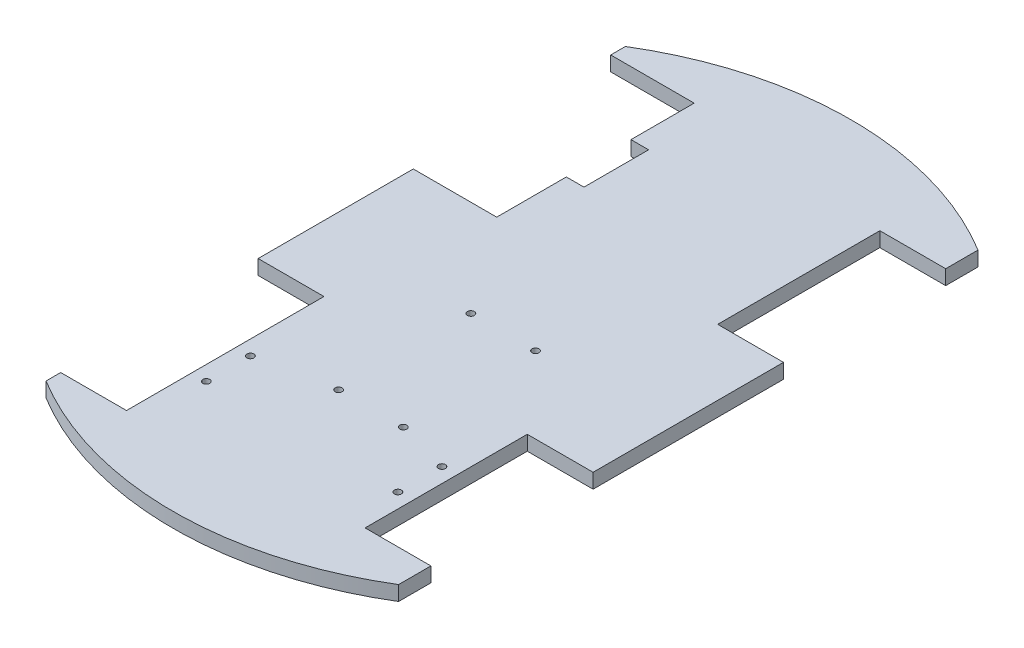
SolidWorks part; units mm, degrees
material "Oak"
ref_plane "Front Plane" through (0, 0, 0) normal (0, 0, 1) x (1, 0, 0)
ref_plane "Top Plane" through (0, 0, 0) normal (0, 1, 0) x (1, 0, 0)
ref_plane "Right Plane" through (0, 0, 0) normal (1, 0, 0) x (0, 0, -1)
sketch "Sketch1" plane through (0, 0, 0) normal (0, 1, 0) x (1, 0, 0)
  line L0 (50.292, 32.512) -> (76.2, 32.512) construction
  line L1 (-76.2, 32.512) -> (-50.292, 32.512) construction
  line L2 (-76.2, 32.512) -> (-76.2, -32.512) construction
  line L3 (-76.2, -32.512) -> (-50.292, -32.512) construction
  line L4 (-50.292, 32.512) -> (-50.292, -32.512) construction
  line L5 (-76.2, 32.512) -> (-50.292, -32.512) construction
  line L6 (-76.2, -32.512) -> (-50.292, 32.512) construction
  line L7 (50.292, 32.512) -> (50.292, -32.512) construction
  line L8 (50.292, -32.512) -> (76.2, -32.512) construction
  line L9 (76.2, 32.512) -> (76.2, -32.512) construction
  line L10 (50.292, 32.512) -> (76.2, -32.512) construction
  line L11 (50.292, -32.512) -> (76.2, 32.512) construction
  line L12 (-76.2, -119.888) -> (-50.292, -119.888) construction
  line L13 (-76.2, -119.888) -> (-76.2, -184.912) construction
  line L14 (-76.2, -184.912) -> (-50.292, -184.912) construction
  line L15 (-50.292, -119.888) -> (-50.292, -184.912) construction
  line L16 (-76.2, -119.888) -> (-50.292, -184.912) construction
  line L17 (-76.2, -184.912) -> (-50.292, -119.888) construction
  line L18 (50.292, -119.888) -> (76.2, -119.888) construction
  line L19 (50.292, -119.888) -> (50.292, -184.912) construction
  line L20 (50.292, -184.912) -> (76.2, -184.912) construction
  line L21 (76.2, -119.888) -> (76.2, -184.912) construction
  line L22 (50.292, -119.888) -> (76.2, -184.912) construction
  line L23 (50.292, -184.912) -> (76.2, -119.888) construction
  line L24 (-76.2, -42.672) -> (-40.132, -42.672)
  line L25 (-76.2, 0) -> (76.2, 0) construction
  line L26 (-76.2, 0) -> (-76.2, -152.4) construction
  line L27 (-76.2, -152.4) -> (76.2, -152.4) construction
  line L28 (76.2, 0) -> (76.2, -152.4) construction
  line L29 (-76.2, 0) -> (76.2, -152.4) construction
  line L30 (-76.2, -152.4) -> (76.2, 0) construction
  line L31 (-40.132, 42.672) -> (-40.132, -42.672)
  line L32 (-76.2, 42.672) -> (-40.132, 42.672)
  line L33 (47.752, -35.052) -> (76.2, -35.052)
  line L34 (47.752, 35.052) -> (47.752, -35.052)
  line L35 (47.752, 35.052) -> (76.2, 35.052)
  line L36 (47.752, -187.452) -> (76.2, -187.452)
  line L37 (47.752, -117.348) -> (47.752, -187.452)
  line L38 (47.752, -117.348) -> (76.2, -117.348)
  line L39 (-76.2, -195.072) -> (-47.752, -195.072)
  line L40 (-47.752, -109.728) -> (-47.752, -195.072)
  line L41 (-76.2, -109.728) -> (-47.752, -109.728)
  line L42 (-76.2, -109.728) -> (-76.2, -42.672)
  line L43 (76.2, -35.052) -> (76.2, -117.348)
  line L44 (-76.2, 42.672) -> (-76.2, 49.022)
  line L45 (76.2, 35.052) -> (76.2, 49.022)
  line L46 (-76.2, -195.072) -> (-76.2, -201.422)
  line L47 (76.2, -187.452) -> (76.2, -201.422)
  line L48 (0, 0) -> (0, 19.7922) construction
  line L49 (-32.512, 15.3535) -> (-40.132, 15.3535)
  line L50 (-32.512, 15.3535) -> (-32.512, -12.5865)
  line L51 (-32.512, -12.5865) -> (-40.132, -12.5865)
  line L52 (-40.132, 15.3535) -> (-40.132, -12.5865)
  line L53 (-32.512, 15.3535) -> (-40.132, -12.5865) construction
  line L54 (-32.512, -12.5865) -> (-40.132, 15.3535) construction
  line L55 (32.512, -12.5865) -> (40.132, -12.5865)
  line L56 (32.512, 15.3535) -> (32.512, -12.5865)
  line L57 (32.512, 15.3535) -> (40.132, 15.3535)
  arc A0 (-76.2, 49.022) -> (76.2, 49.022) centre (0, -76.2) cw
  arc A1 (-76.2, -201.422) -> (76.2, -201.422) centre (0, -76.2) ccw
  point P4 (-63.246, 0)
  point P9 (63.246, 0)
  point P14 (-63.246, -152.4)
  point P19 (63.246, -152.4)
  point P24 (0, -76.2)
  point P52 (-36.322, 1.3835)
  dimension "D7" = 6.35
  dimension "D8" = 7.62
  dimension "D12" = 146.5844
  dimension "D1" = 152.4
  dimension "D2" = 152.4
  dimension "D3" = 25.908
  dimension "D4" = 65.024
  dimension "D6" = 2.54
  dimension "D9" = 27.94
  dimension "D10" = 10.16
  dimension "D5" = 10.16
  dimension "D11" = 10.16
  dimension "D13" = 2.54
  dimension "D14" = 67.056
  dimension "D15" = 28.448
  dimension "D16" = 77.5894
extrude "Chassis" add sketch "Sketch1" along normal blind 6.35 contours L46 A1 L47 L36 L37 L38 L43 L33 L34 L55 L56 L57 L35 L45 A0 L44 L32 L31 L49 L50 L51 L24 L42 L41 L40 L39 region at (2.7397, 0, 78.2102)
sketch "Sketch2" plane through (0, 6.35, 0) normal (0, 1, 0) x (1, 0, 0)
  line L0 (-47.752, -109.728) -> (-47.752, -195.072) construction
  line L1 (-76.2, -109.728) -> (-47.752, -109.728) construction
  circle A0 centre (18.288, -84.328) radius 1.5
  circle A1 centre (-9.652, -84.328) radius 1.5
  circle A2 centre (-9.652, -141.478) radius 1.5
  circle A3 centre (18.288, -141.478) radius 1.5
  dimension "D1" = 3
  dimension "D2" = 3
  dimension "D3" = 3
  dimension "D4" = 3
  dimension "D5" = 57.15
  dimension "D6" = 27.94
  dimension "D7" = 38.1
  dimension "D8" = 31.75
extrude "Cut-Extrude1" cut sketch "Sketch2" against normal blind 12.7
sketch "Sketch3" plane through (0, 6.35, 0) normal (0, 1, 0) x (1, 0, 0)
  circle A0 centre (-41.402, -147.875) radius 1.5
  circle A1 centre (-41.402, -166.925) radius 1.5
  circle A2 centre (41.402, -166.925) radius 1.5
  circle A3 centre (41.402, -147.875) radius 1.5
  dimension "D1" = 3
  dimension "D2" = 3
  dimension "D3" = 3
  dimension "D4" = 3
extrude "Cut-Extrude2" cut sketch "Sketch3" against normal through all
